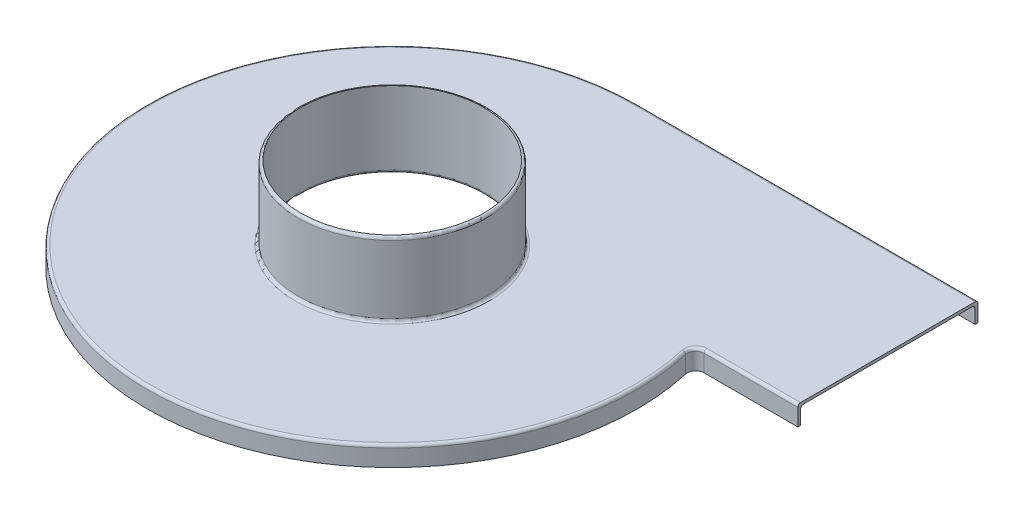
SolidWorks part; units mm, degrees
ref_plane "Front Plane" through (0, 0, 0) normal (0, 0, 1) x (1, 0, 0)
ref_plane "Top Plane" through (0, 0, 0) normal (0, 1, 0) x (1, 0, 0)
ref_plane "Right Plane" through (0, 0, 0) normal (1, 0, 0) x (0, 0, -1)
sketch "Sketch1" plane through (0, 0, 0) normal (0, 1, 0) x (1, 0, 0)
  line L3 (121, 24) -> (87.7496, 24)
  line L5 (0, 86) -> (121, 86)
  line L9 (121, 23) -> (87.7496, 23)
  line L10 (121, 25) -> (121, 85)
  line L11 (0, 87) -> (121, 87)
  line L12 (121, 87) -> (121, 23)
  arc A2 (0, 86) -> (83.8497, 19.1111) centre (0, 0) ccw
  arc A3 (87.7496, 24) -> (83.8497, 19.1111) centre (87.7496, 20) ccw
  arc A4 (87.7496, 23) -> (84.8247, 19.3333) centre (87.7496, 20) ccw
  arc A5 (0, 87) -> (84.8247, 19.3333) centre (0, 0) ccw
  dimension "D1" = 1
extrude "Boss-Extrude1" add sketch "Sketch1" along normal blind 1 contours A3 L3 L5 A2 | L11 A5 A4 L9 L12 L3 A3 A2 L5 region at (118.2882, 0, -23.5) region at (12.1908, 0, -8.3425)
extrude "Boss-Extrude2" add sketch "Sketch1<3>" against normal blind 6 contours L11 A5 A4 L9 L12 L3 A3 A2 L5 region at (118.2882, 0, -23.5)
sketch "Sketch1<3>" plane through (0, 0, 0) normal (0, 1, 0) x (1, 0, 0) same geometry as "Sketch1"
sketch "Sketch4" plane through (0, 1, 0) normal (0, 1, 0) x (1, 0, 0)
  circle A0 centre (0, 0) radius 33.5
  circle A1 centre (0, 0) radius 32.5
  dimension "D1" = 67
  dimension "D2" = 1
extrude "Boss-Extrude3" add sketch "Sketch4" along normal blind 26 contours A1 | A0 A1 region at (-32.5525, 1, 0) region at (0, 1, 0)
extrude "Cut-Extrude3" cut sketch "Sketch4<4>" along normal up to surface (26 mm away) from offset 1 contours A1 region at (0, 1, 0) up to face at (0, 27, 33.5) offset against normal yes
sketch "Sketch4<4>" plane through (0, 1, 0) normal (0, 1, 0) x (1, 0, 0) same geometry as "Sketch4"
fillet "Fillet2" radius 1 11 edges at (0, 0, 32.5) (0, 27, 33.5) (0, 1, 33.5) (104.3748, 1, -23) (85.4044, 1, -21.8708) (-54.254, 1, 68.011) (60.5, 0, -86) (104.3748, 0, -24) (84.6227, 0, -22.4944) (60.5, 1, -87) (-53.6304, 0, 67.2293)
